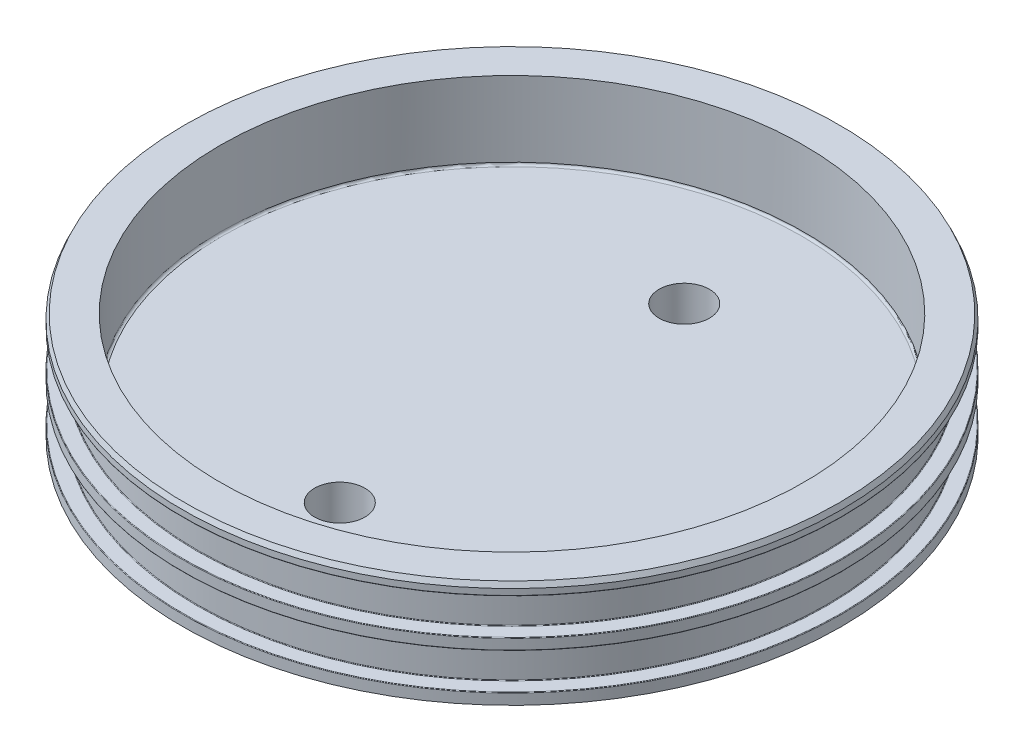
SolidWorks part; units mm, degrees
material "6061-T6 (SS)"
ref_plane "Front Plane" through (0, 0, 0) normal (0, 0, 1) x (1, 0, 0)
ref_plane "Top Plane" through (0, 0, 0) normal (0, 1, 0) x (1, 0, 0)
ref_plane "Right Plane" through (0, 0, 0) normal (1, 0, 0) x (0, 0, -1)
sketch "Sketch1" plane through (0, 0, 0) normal (0, 0, 1) x (1, 0, 0)
  line L0 (0, 48.1922) -> (0, -25.6743) construction
  line L1 (0, 0) -> (72.898, 0)
  line L2 (72.898, 0) -> (72.898, 2.4638)
  line L3 (72.898, 2.4638) -> (69.6468, 2.4638)
  line L4 (69.6468, 2.4638) -> (69.6468, 10.4648)
  line L5 (69.6468, 10.4648) -> (72.898, 10.4648)
  line L6 (72.898, 10.4648) -> (72.898, 12.9286)
  line L7 (72.898, 12.9286) -> (69.6468, 12.9286)
  line L8 (64.5668, 23.4696) -> (64.5668, 6.35)
  line L9 (64.5668, 6.35) -> (0, 6.35)
  line L10 (0, 6.35) -> (0, 0)
  line L11 (69.6468, 12.9286) -> (69.6468, 20.9296)
  line L12 (69.6468, 20.9296) -> (72.898, 20.9296)
  line L13 (72.898, 20.9296) -> (72.898, 23.4696)
  line L14 (72.898, 23.4696) -> (64.5668, 23.4696)
  dimension "D1" = 145.796
  dimension "D2" = 8.001
  dimension "D5" = 6.35
  dimension "D7" = 8.001
  dimension "D4" = 2.4638
  dimension "D8" = 2.54
  dimension "D3" = 69.6468
  dimension "D6" = 5.08
revolve "Revolve1" add sketch "Sketch1" angle 360 about L0
sketch "Sketch6" plane through (0, 0, 0) normal (0, -1, 0) x (1, 0, 0)
  circle A0 centre (0, 0) radius 66.04
  dimension "D1" = 132.08
extrude "Boss-Extrude1" add sketch "Sketch6" along normal blind 2.54
hole_wizard "Pipe Tap Drill for 1/4 Tap - GN2" positions "Sketch2" profile "Sketch3" hole size "1/4" standard "ANSI Inch" end condition through all
sketch "Sketch2" plane through (0, 6.35, 0) normal (0, 1, 0) x (1, 0, 0)
  point P4 (0, -38.1)
  point P13 (0, 0)
  point P14 (0, -38.1)
  dimension "D1" = 38.1
sketch "Sketch3" plane through (0, 6.35, 38.1) normal (1, 0, 0) x (0, 0, 1)
  line L0 (0, 0) -> (0, 8.89)
  line L1 (0, 8.89) -> (5.5626, 8.89)
  line L2 (5.5626, 8.89) -> (5.5626, 0)
  line L5 (5.5626, 0) -> (0, 0)
  line L11 (0, -6.35) -> (0, 107.95) construction
  dimension "Thru Hole Dia." = 11.1252
  dimension "Thru Hole Depth" = 8.89
fillet "CNC ID Fillet" radius 0.127 5 edges at (-69.6468, 10.4648, 0) (-69.6468, 2.4638, 0) (-69.6468, 20.9296, 0) (-69.6468, 12.9286, 0) (66.04, 0, 0)
fillet "CNC OD Fillet" radius 0.127 5 edges at (-72.898, 10.4648, 0) (-72.898, 2.4638, 0) (66.04, -2.54, 0) (-72.898, 20.9296, 0) (-72.898, 12.9286, 0)
chamfer "CNC Chamfers" distance 0.508 angle 65 1 edges at (-72.898, 23.4696, 0) first distance on face at (-64.5668, 23.4696, 0)
fillet "CNC Bore Fillet" radius 0.508 1 edges at (-64.5668, 6.35, 0)
hole_wizard "Pipe Tap Drill for 1/4 Tap - Relief Valve" positions "Sketch13" profile "Sketch14" hole size "1/4" standard "ANSI Inch" end condition through all
sketch "Sketch13" plane through (0, -2.54, 0) normal (0, -1, 0) x (-1, 0, 0)
  point P4 (0, 38.1)
  dimension "D1" = 38.1
sketch "Sketch14" plane through (0, -2.54, -38.1) normal (1, 0, 0) x (0, 0, -1)
  line L0 (0, 0) -> (0, 26.0096)
  line L1 (0, 26.0096) -> (5.5626, 26.0096)
  line L2 (5.5626, 26.0096) -> (5.5626, 0)
  line L5 (5.5626, 0) -> (0, 0)
  line L11 (0, -6.35) -> (0, 107.95) construction
  dimension "Thru Hole Dia." = 11.1252
  dimension "Thru Hole Depth" = 26.0096
equation "\"D3@Sketch1\"=5.484/2"
